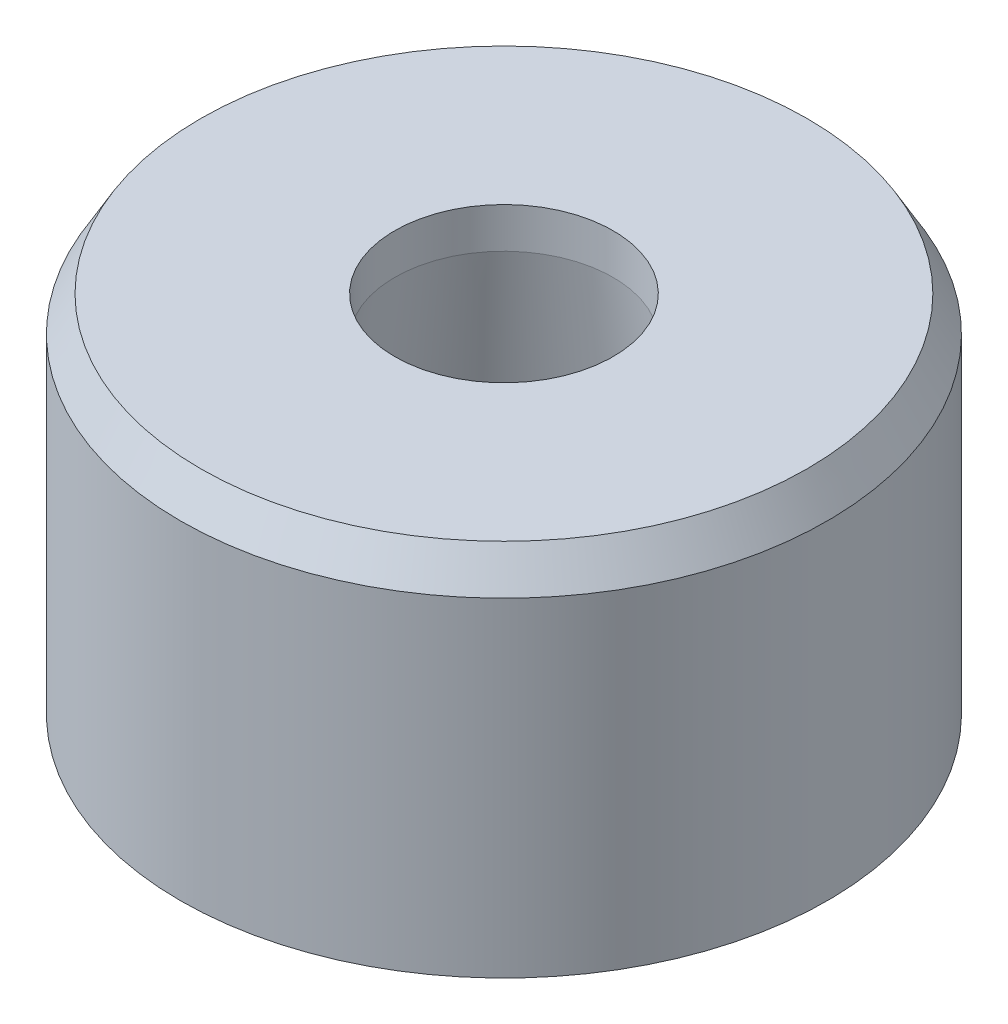
SolidWorks part; units mm, degrees
ref_plane "Front" through (0, 0, 0) normal (0, 0, 1) x (1, 0, 0)
ref_plane "Top" through (0, 0, 0) normal (0, 1, 0) x (1, 0, 0)
ref_plane "Right" through (0, 0, 0) normal (1, 0, 0) x (0, 0, -1)
sketch "Sketch1" plane through (0, 0, 0) normal (0, 1, 0) x (1, 0, 0)
  circle A0 centre (0, 0) radius 2.7
  circle A1 centre (0, 0) radius 8
  dimension "D1" = 5.4
  dimension "D2" = 16
extrude "Boss-Extrude1" add sketch "Sketch1" along normal blind 9
chamfer "Chamfer1" distance 8 angle 8 1 edges at (0, 0, 2.7) first distance on face at (0, 9, 2.7)
chamfer "Chamfer2" distance 0.5 angle 60 1 edges at (0, 9, 8) first distance on face at (0, 9, 8)
equation "\"height\" = 13 - 4"
equation "\"D1@Boss-Extrude1\"=\"height\""
